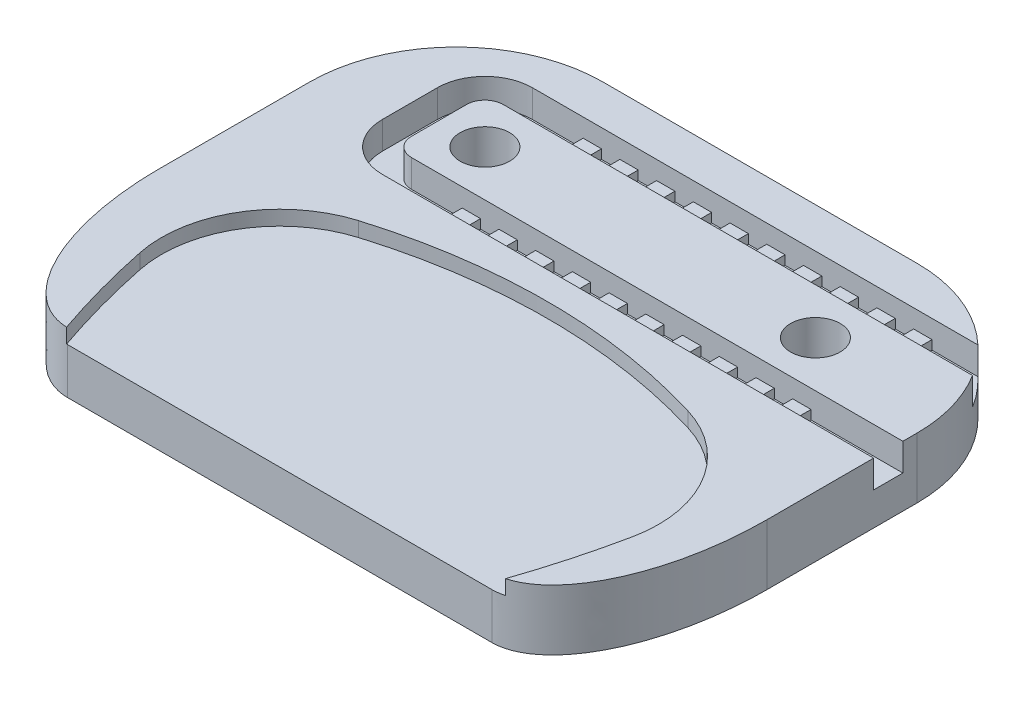
SolidWorks part; units mm, degrees
ref_plane "Front Plane" through (0, 0, 0) normal (0, 0, 1) x (1, 0, 0)
ref_plane "Top Plane" through (0, 0, 0) normal (0, 1, 0) x (1, 0, 0)
ref_plane "Right Plane" through (0, 0, 0) normal (1, 0, 0) x (0, 0, -1)
sketch "Pick" plane through (0, 0, 0) normal (0, 1, 0) x (1, 0, 0)
  line L0 (0, 0) -> (0, 30.62) construction
  line L1 (-13.11, 22.1848) -> (0, 22.1848) construction
  line L2 (0, 22.1848) -> (13.11, 22.1848) construction
  line L3 (0, 2.9) -> (-2.9, 2.9) construction
  line L6 (9.0762, 10.7993) -> (9.4821, 11.5846) construction
  line L7 (-7.0973, 23.4286) -> (-12.0562, 27.0493) construction
  arc A0 (-8.8774, 29.3049) -> (8.8774, 29.3049) centre (0, 0) cw
  arc A1 (-2.1219, 0.9232) -> (-13.11, 22.1848) centre (30.3499, 31.175) cw
  arc A2 (-13.11, 22.1848) -> (-8.8774, 29.3049) centre (-7.0973, 23.4286) cw
  arc A3 (2.1219, 0.9232) -> (13.11, 22.1848) centre (-30.3499, 31.175) ccw
  arc A4 (13.11, 22.1848) -> (8.8774, 29.3049) centre (7.0973, 23.4286) ccw
  arc A5 (-2.1219, 0.9232) -> (2.1219, 0.9232) centre (0, 2.9) ccw
  circle A6 centre (-7.0973, 23.4286) radius 6.14 construction
  circle A7 centre (-30.3499, 31.175) radius 44.38 construction
  circle A8 centre (0, 2.9) radius 2.9 construction
  point P8 (0, 30.62)
  dimension "D1" = 30.62
  dimension "D2" = 26.22
  dimension "D3" = 44.38
  dimension "D4" = 6.14
  dimension "D5" = 2.9
sketch "Sketch3" plane through (0, 0, 0) normal (0, 1, 0) x (1, 0, 0)
  line L0 (-11.8929, 16.62) -> (11.8929, 16.62)
  line L1 (-13.11, 22.1848) -> (-14, 26.4873) construction
  line L2 (0, 16.62) -> (0, 22.1848) construction
  line L3 (0, 22.1848) -> (13.11, 22.1848) construction
  line L4 (0, 0) -> (0, 30.62) construction
  line L5 (0, 30.92) -> (0, 30.62) construction
  line L6 (-11.8929, 16.62) -> (-10.1999, 11.7063) construction
  line L7 (-13.11, 22.1848) -> (-13.4038, 22.124) construction
  line L8 (-11.8929, 16.62) -> (-11.6093, 16.7177) construction
  line L9 (-8.8774, 29.3049) -> (-11.642, 28.4674) construction
  line L10 (-8.8774, 29.3049) -> (-8.9644, 29.592) construction
  line L11 (-11.8929, 16.62) -> (-16.8356, 16.62)
  line L12 (-16.8356, 16.62) -> (-16.8356, 42.7863)
  line L13 (-16.8356, 42.7863) -> (16.2633, 42.7863)
  line L14 (16.2633, 42.7863) -> (16.2633, 16.62)
  line L15 (16.2633, 16.62) -> (11.8929, 16.62)
  line L16 (0, 40.595) -> (0, 42.7863) construction
  line L17 (0, 30.62) -> (0, 22.1848) construction
  line L33 (16.2633, 32.42) -> (-10.5, 32.42)
  line L34 (-13.0875, 35.0075) -> (-13.0875, 38.0075)
  line L35 (-11.5, 35.0075) -> (-11.5, 38.0075)
  line L36 (-10.5, 34.0075) -> (16.2633, 34.0075)
  line L37 (16.2633, 34.0075) -> (16.2633, 32.42)
  line L38 (-10.5, 39.0075) -> (16.2633, 39.0075)
  line L39 (16.2633, 39.0075) -> (16.2633, 40.595)
  line L40 (16.2633, 40.595) -> (-10.5, 40.595)
  line L41 (-13.0875, 35.0075) -> (-11.5, 35.0075) construction
  line L42 (-11.5, 38.0075) -> (-13.0875, 38.0075) construction
  line L43 (0, 30.92) -> (0, 32.42) construction
  line L44 (0, 34.0075) -> (0, 36.5075) construction
  line L45 (-9, 36.5075) -> (9, 36.5075) construction
  line L46 (-9, 36.5075) -> (-11.5, 36.5075) construction
  line L47 (0, 36.5075) -> (0, 39.0075) construction
  arc A0 (-11.8929, 16.62) -> (-13.4038, 22.124) centre (30.3499, 31.175) cw
  arc A1 (2.1219, 0.9232) -> (13.11, 22.1848) centre (-30.3499, 31.175) ccw construction
  arc A2 (11.8929, 16.62) -> (13.4038, 22.124) centre (-30.3499, 31.175) ccw
  arc A3 (-8.9644, 29.592) -> (8.9644, 29.592) centre (0, 0) cw
  arc A4 (-13.11, 22.1848) -> (-2.1219, 0.9232) centre (30.3499, 31.175) ccw construction
  arc A5 (8.8774, 29.3049) -> (-8.8774, 29.3049) centre (0, 0) ccw construction
  arc A7 (-13.4038, 22.124) -> (-8.9644, 29.592) centre (-7.0973, 23.4286) cw
  arc A8 (8.9644, 29.592) -> (13.4038, 22.124) centre (7.0973, 23.4286) cw
  arc A12 (-10.5, 34.0075) -> (-11.5, 35.0075) centre (-10.5, 35.0075) cw
  arc A13 (-10.5, 32.42) -> (-13.0875, 35.0075) centre (-10.5, 35.0075) cw
  arc A14 (-11.5, 38.0075) -> (-10.5, 39.0075) centre (-10.5, 38.0075) cw
  arc A15 (-10.5, 40.595) -> (-13.0875, 38.0075) centre (-10.5, 38.0075) ccw
  point P26 (-9, 36.5075)
  point P42 (9, 36.5075)
  point P95 (0, 36.5075)
  dimension "D2" = 0.3
  dimension "D3" = 18
  dimension "D7" = 1
  dimension "D1" = 14
  dimension "D4" = 6.2788
  dimension "D5" = 16.2633
  dimension "D6" = 33.0989
  dimension "D8" = 1.5875
  dimension "D9" = 1.5
  dimension "D10" = 2.5
extrude "Boss-Extrude1" add sketch "Sketch3" against normal blind 0.8 contours A3 A8 A2 L15 L14 L13 L12 L11 A0 A7 | L40 A15 L34 A13 L33 L14 L36 A12 L35 A14 L38 | A14 L35 A12 L36 L14 L38 region at (-2.3245, 0, -31.7034) region at (2.8816, 0, -32.7247) region at (2.424, 0, -36.5075)
extrude "Boss-Extrude4" add sketch "Sketch3<5>" against normal blind 2.5 from surface contours A3 A8 A2 L15 L14 L13 L12 L11 A0 A7 | A8 A3 A7 A0 L0 A2 | L40 A15 L34 A13 L33 L14 L36 A12 L35 A14 L38 | A14 L35 A12 L36 L14 L38 region at (0, 0, -23.3328) region at (-2.3245, 0, -31.7034) region at (2.8816, 0, -32.7247) region at (2.424, 0, -36.5075) starting at face at (-0.1145, -0.8, -25.8487)
sketch "Sketch3<5>" plane through (0, 0, 0) normal (0, 1, 0) x (1, 0, 0) same geometry as "Sketch3"
extrude "Cut-Extrude2" cut sketch "Sketch3<7>" against normal blind 1.5 contours L40 A15 L34 A13 L33 L14 L36 A12 L35 A14 L38 region at (2.8816, 0, -32.7247)
sketch "Sketch3<7>" plane through (0, 0, 0) normal (0, 1, 0) x (1, 0, 0) same geometry as "Sketch3"
hole_wizard "M2.5 Clearance Hole1" positions "Sketch6" profile "Sketch7" hole size "M2.5" standard "ANSI Metric"
sketch "Sketch6" plane through (0, 0, 0) normal (0, 1, 0) x (1, 0, 0)
  point P0 (-9, 36.5075)
  point P3 (9, 36.5075)
sketch "Sketch7" plane through (-9, 0, -36.5075) normal (1, 0, 0) x (0, 0, 1)
  line L0 (0, 0) -> (0, 12)
  line L1 (0, 12) -> (1.35, 11.1888)
  line L2 (1.35, 11.1888) -> (1.35, 0)
  line L5 (1.35, 0) -> (0, 0)
  line L10 (0, 12) -> (-1.35, 11.1888) construction
  line L11 (0, -6.35) -> (0, 107.95) construction
  dimension "Hole Dia." = 2.7
  dimension "Hole Depth" = 12
  dimension "Drill Angle" = 118
sketch "Sketch11" plane through (0, 0, 0) normal (0, 1, 0) x (1, 0, 0)
  line L12 (16.2633, 40.595) -> (-10.5, 40.595) construction
  line L13 (11.2633, 40.595) -> (10.2633, 40.595)
  line L14 (11.2633, 40.595) -> (11.2633, 39.0075)
  line L15 (11.2633, 39.0075) -> (10.2633, 39.0075)
  line L16 (10.2633, 40.595) -> (10.2633, 39.0075)
  line L17 (-10.5, 39.0075) -> (16.2633, 39.0075) construction
  line L18 (-10.5, 34.0075) -> (16.2633, 34.0075) construction
  line L19 (11.2633, 34.0075) -> (10.2633, 34.0075)
  line L20 (11.2633, 34.0075) -> (11.2633, 32.42)
  line L21 (11.2633, 32.42) -> (10.2633, 32.42)
  line L22 (10.2633, 34.0075) -> (10.2633, 32.42)
  line L23 (16.2633, 32.42) -> (-10.5, 32.42) construction
  line L24 (16.2633, 42.7863) -> (16.2633, 16.62) construction
  line L27 (10.2633, 39.0075) -> (10.2633, 34.0075) construction
  line L33 (-8.8774, 29.3049) -> (8.8774, 29.3049) construction
  line L34 (0, 30.62) -> (0, 22.1848) construction
  line L35 (0, 29.3049) -> (0, 30.92) construction
  point P47 (0, 29.3049)
  dimension "D1" = 5
  dimension "D2" = 1
extrude "Boss-Extrude7" add sketch "Sketch11" along normal blind 0.5 from surface contours L13 L16 L15 L14 | L19 L22 L21 L20 region at (10.7633, 0, -39.8013) region at (10.7633, 0, -33.2138) starting at face at (-2.3007, -1.5, -36.5075)
pattern_linear "LPattern2" count 10 spacing 2 along (-1, 0, 0) of "Boss-Extrude7"
fillet "Fillet4" radius 8 2 edges at (16.2633, -1.65, -42.7863) (-16.8356, -1.65, -42.7863)
fillet "Fillet6" radius 10 1 edges at (16.2633, -1.65, -16.62) second distance 5 first distance on face at (16.2633, -1.2, -29.4584)
fillet "Fillet7" radius 5 1 edges at (-16.8356, -1.65, -16.62) second distance 10 first distance on face at (-1.5505, -1.575, -16.62)
